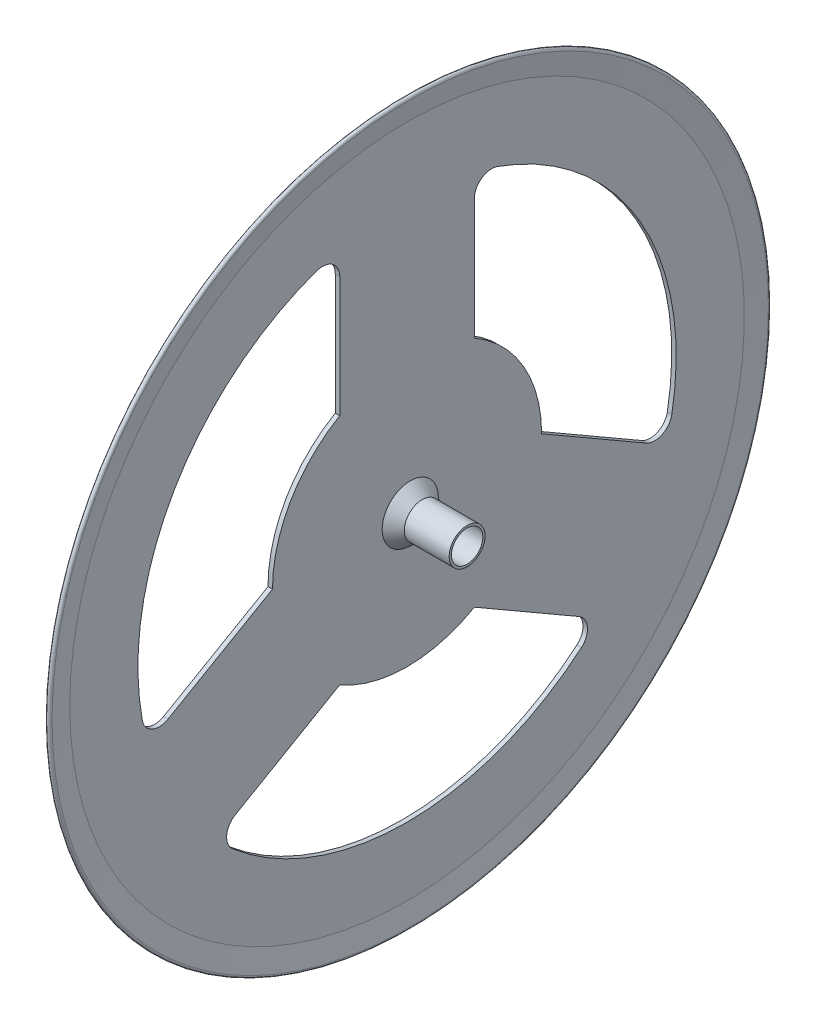
SolidWorks part; units mm, degrees
ref_plane "Front Plane" through (0, 0, 0) normal (0, 0, 1) x (1, 0, 0)
ref_plane "Top Plane" through (0, 0, 0) normal (0, 1, 0) x (1, 0, 0)
ref_plane "Right Plane" through (0, 0, 0) normal (1, 0, 0) x (0, 0, -1)
sketch "Sketch1" plane through (0, 0, 0) normal (0, 0, 1) x (1, 0, 0)
  line L0 (0, 0) -> (-75.2862, 0) construction
  line L1 (-22.4009, 0) -> (-22.4009, 75.2707)
  line L2 (-22.4009, 75.2707) -> (-21.6835, 80)
  line L3 (-21.4009, 0) -> (-21.4009, 75.1953)
  line L4 (-21.4009, 75.1953) -> (-20.6948, 79.85)
  line L5 (-22.4009, 0) -> (-21.4009, 0)
  arc A1 (-21.6835, 80) -> (-20.6948, 79.85) centre (-21.1892, 79.925) cw
  point P9 (-22.4009, 75.1953)
  dimension "D1" = 160
  dimension "D2" = 1
revolve "Revolve1" add sketch "Sketch1" angle 360 about L5
sketch "Sketch2" plane through (-21.4009, 0, 0) normal (1, 0, 0) x (0, 0, -1)
  line L0 (0, 0) -> (0, 96.337) construction
  line L1 (-15, 52.8705) -> (-15, 25.9808)
  line L2 (15, 52.8705) -> (15, 25.9808)
  line L3 (53.2872, -13.4449) -> (30, 0)
  line L4 (38.2872, -39.4256) -> (15, -25.9808)
  line L5 (-38.2872, -39.4256) -> (-15, -25.9808)
  line L6 (-53.2872, -13.4449) -> (-30, 0)
  circle A0 centre (0, 0) radius 30
  arc A1 (-20.1635, 56.5105) -> (20.1635, 56.5105) centre (0, 0) ccw
  arc A2 (-20.1635, 56.5105) -> (-15, 52.8705) centre (-18.8648, 52.8705) cw
  arc A3 (20.1635, 56.5105) -> (15, 52.8705) centre (18.8648, 52.8705) ccw
  arc A4 (59.0213, -10.7931) -> (53.2872, -13.4449) centre (55.2195, -10.0979) cw
  arc A5 (38.8577, -45.7174) -> (38.2872, -39.4256) centre (36.3548, -42.7726) ccw
  arc A6 (-38.8577, -45.7174) -> (-38.2872, -39.4256) centre (-36.3548, -42.7726) cw
  arc A7 (-59.0213, -10.7931) -> (-53.2872, -13.4449) centre (-55.2195, -10.0979) ccw
  dimension "D1" = 120
  dimension "D2" = 60
  dimension "D3" = 3
extrude "Cut-Extrude1" cut sketch "Sketch2" against normal through all contours A1 A7 L6 A0 L1 A2 | A6 A1 A5 L4 A0 L5 | A4 A1 A3 L2 A0 L3 region at (-21.4009, 21.7165, 37.6141) region at (-21.4009, 21.7165, -37.6141) region at (-21.4009, -43.433, 0)
sketch "Sketch4" plane through (0, 0, 0) normal (0, 0, 1) x (1, 0, 0)
  line L0 (-20.6948, 0) -> (4.3387, 0) construction
  line L1 (-20.6948, 79.85) -> (-20.6948, -79.85) construction
  line L2 (-20.6948, 6.2549) -> (-18.0107, 4)
  line L3 (-18.0107, 4) -> (-8.0107, 4)
  line L4 (-8.0107, 4) -> (-8.0107, 0)
  line L5 (-8.0107, 0) -> (-20.6948, 0)
  line L6 (-20.6948, 0) -> (-20.6948, 6.2549)
  dimension "D1" = 10
  dimension "D2" = 8
revolve "Revolve2" add sketch "Sketch4" angle 360 about L0
sketch "Sketch5" plane through (-8.0107, 0, 0) normal (1, 0, 0) x (0, 0, -1)
  circle A0 centre (0, 0) radius 3.5
  dimension "D1" = 7
extrude "Cut-Extrude2" cut sketch "Sketch5" against normal blind 8 contours A0
